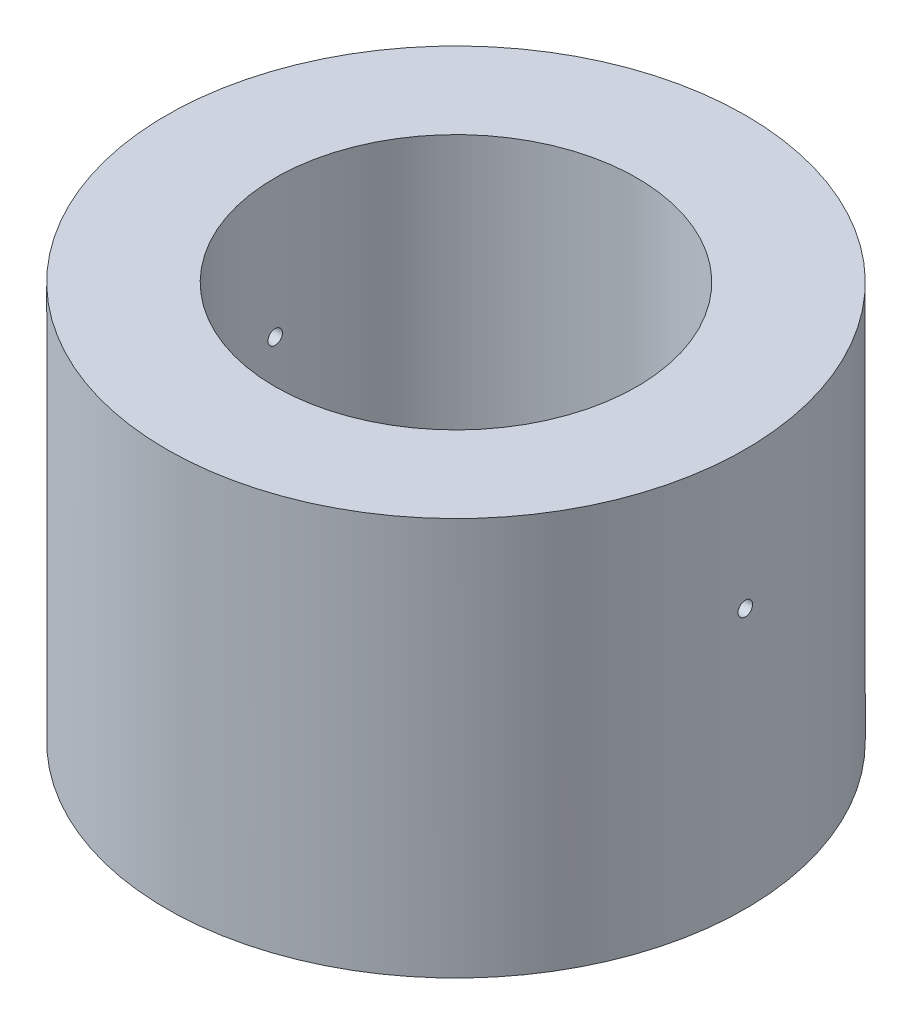
SolidWorks part; units mm, degrees
material "C (Graphite)"
ref_plane "Front Plane" through (0, 0, 0) normal (0, 0, 1) x (1, 0, 0)
ref_plane "Top Plane" through (0, 0, 0) normal (0, 1, 0) x (1, 0, 0)
ref_plane "Right Plane" through (0, 0, 0) normal (1, 0, 0) x (0, 0, -1)
sketch "Sketch1" plane through (0, 0, 0) normal (0, 1, 0) x (1, 0, 0)
  circle A0 centre (0, 0) radius 40
  circle A1 centre (0, 0) radius 25
  dimension "D1" = 80
  dimension "D2" = 50
extrude "Boss-Extrude1" add sketch "Sketch1" along normal blind 50
sketch "Sketch2" plane through (0, 0, 0) normal (0, -1, 0) x (1, 0, 0)
  circle A0 centre (0, 0) radius 37.5
  circle A1 centre (0, 0) radius 40
  dimension "D1" = 75
  dimension "D2" = 80
sketch "Sketch3" plane through (0, 0, 0) normal (1, 0, 0) x (0, 0, -1)
  line L0 (40, 50) -> (-40, 50) construction
  circle A0 centre (0, 30.95) radius 1
  dimension "D1" = 2
  dimension "D2" = 19.05
extrude "Cut-Extrude2" cut sketch "Sketch3" against normal through all both and the other way through all
extrude "Boss-Extrude2" add sketch "Sketch2" along normal blind 5
